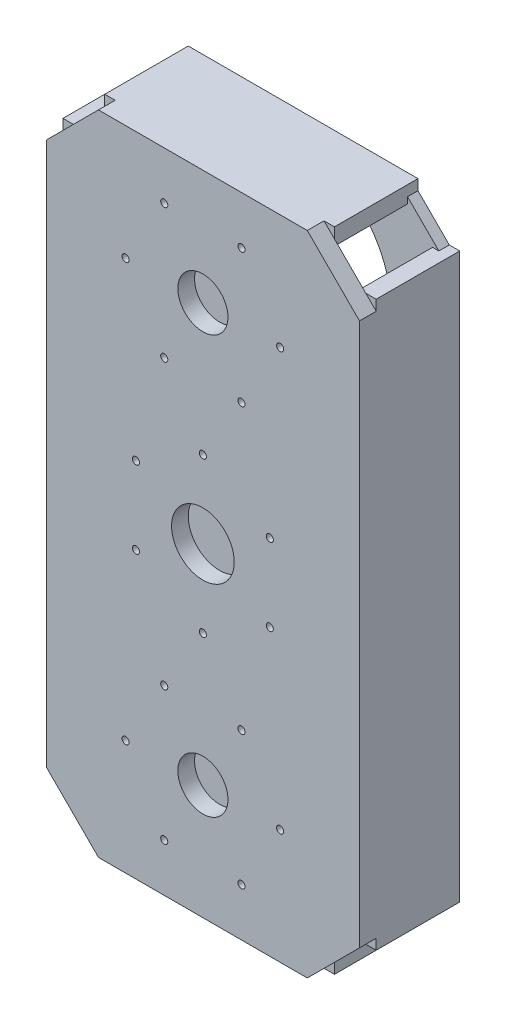
SolidWorks part; units mm, degrees
ref_plane "Front Plane" through (0, 0, 0) normal (0, 0, 1) x (1, 0, 0)
ref_plane "Top Plane" through (0, 0, 0) normal (0, 1, 0) x (1, 0, 0)
ref_plane "Right Plane" through (0, 0, 0) normal (1, 0, 0) x (0, 0, -1)
ref_plane "PL_Top_Plate_base" through (0, 0, 131) normal (0, 0, 1) x (1, 0, 0)
sketch "SK_Top_Plate" plane through (0, 0, 131) normal (0, 0, 1) x (1, 0, 0)
  line L0 (-50, -155) -> (50, -155)
  line L1 (50, -155) -> (75, -130)
  line L2 (75, -130) -> (75, 130)
  line L3 (75, 130) -> (50, 155)
  line L4 (50, 155) -> (-50, 155)
  line L5 (-50, 155) -> (-75, 130)
  line L6 (-75, 130) -> (-75, -130)
  line L7 (-75, -130) -> (-50, -155)
  circle A0 centre (37, 100) radius 1.7
  circle A1 centre (18.5, 132.0429) radius 1.7
  circle A2 centre (-18.5, 132.0429) radius 1.7
  circle A3 centre (-37, 100) radius 1.7
  circle A4 centre (-18.5, 67.9571) radius 1.7
  circle A5 centre (18.5, 67.9571) radius 1.7
  circle A6 centre (0, 100) radius 12
  circle A7 centre (37, -100) radius 1.7
  circle A8 centre (18.5, -67.9571) radius 1.7
  circle A9 centre (-18.5, -67.9571) radius 1.7
  circle A10 centre (-37, -100) radius 1.7
  circle A11 centre (-18.5, -132.0429) radius 1.7
  circle A12 centre (18.5, -132.0429) radius 1.7
  circle A13 centre (0, -100) radius 12
  circle A14 centre (32.0429, 18.5) radius 1.7
  circle A15 centre (0, 37) radius 1.7
  circle A16 centre (-32.0429, 18.5) radius 1.7
  circle A17 centre (-32.0429, -18.5) radius 1.7
  circle A18 centre (0, -37) radius 1.7
  circle A19 centre (32.0429, -18.5) radius 1.7
  circle A20 centre (0, 0) radius 15
  dimension "D17_SK_Top_Plate" = 3.4
  dimension "D20_SK_Top_Plate" = 3.4
  dimension "D23_SK_Top_Plate" = 3.4
  dimension "D26_SK_Top_Plate" = 3.4
  dimension "D29_SK_Top_Plate" = 3.4
  dimension "D32_SK_Top_Plate" = 3.4
  dimension "D35_SK_Top_Plate" = 24
  dimension "D37_SK_Top_Plate" = 3.4
  dimension "D40_SK_Top_Plate" = 3.4
  dimension "D43_SK_Top_Plate" = 3.4
  dimension "D46_SK_Top_Plate" = 3.4
  dimension "D49_SK_Top_Plate" = 3.4
  dimension "D52_SK_Top_Plate" = 3.4
  dimension "D55_SK_Top_Plate" = 24
  dimension "D57_SK_Top_Plate" = 3.4
  dimension "D60_SK_Top_Plate" = 3.4
  dimension "D62_SK_Top_Plate" = 3.4
  dimension "D65_SK_Top_Plate" = 3.4
  dimension "D68_SK_Top_Plate" = 3.4
  dimension "D70_SK_Top_Plate" = 3.4
  dimension "D73_SK_Top_Plate" = 30
  dimension "P1" = 50
  dimension "P2" = 155
  dimension "P3" = 50
  dimension "P4" = 155
  dimension "P5" = 75
  dimension "P6" = 130
  dimension "P7" = 75
  dimension "P8" = 130
  dimension "P9" = 50
  dimension "P10" = 155
  dimension "P11" = 50
  dimension "P12" = 155
  dimension "P13" = 75
  dimension "P14" = 130
  dimension "P15" = 75
  dimension "P16" = 130
  dimension "P18" = 37
  dimension "P19" = 100
  dimension "P21" = 18.5
  dimension "P22" = 132.0429
  dimension "P24" = 18.5
  dimension "P25" = 132.0429
  dimension "P27" = 37
  dimension "P28" = 100
  dimension "P30" = 18.5
  dimension "P31" = 67.9571
  dimension "P33" = 18.5
  dimension "P34" = 67.9571
  dimension "P36" = 100
  dimension "P38" = 37
  dimension "P39" = 100
  dimension "P41" = 18.5
  dimension "P42" = 67.9571
  dimension "P44" = 18.5
  dimension "P45" = 67.9571
  dimension "P47" = 37
  dimension "P48" = 100
  dimension "P50" = 18.5
  dimension "P51" = 132.0429
  dimension "P53" = 18.5
  dimension "P54" = 132.0429
  dimension "P56" = 100
  dimension "P58" = 32.0429
  dimension "P59" = 18.5
  dimension "P61" = 37
  dimension "P63" = 32.0429
  dimension "P64" = 18.5
  dimension "P66" = 32.0429
  dimension "P67" = 18.5
  dimension "P69" = 37
  dimension "P71" = 32.0429
  dimension "P72" = 18.5
extrude "Top_Plate" add sketch "SK_Top_Plate" along normal blind 8
ref_plane "PL_Front_Wall_base" through (67, 0, 0) normal (1, 0, 0) x (0, 0, -1)
sketch "SK_Front_Wall" plane through (67, 0, 0) normal (1, 0, 0) x (0, 0, -1)
  line L0 (-91, -135) -> (-91, 135)
  line L1 (-91, 135) -> (-131, 135)
  line L2 (-131, 135) -> (-131, -135)
  line L3 (-131, -135) -> (-91, -135)
  dimension "P1" = 91
  dimension "P2" = 135
  dimension "P3" = 91
  dimension "P4" = 135
  dimension "P5" = 131
  dimension "P6" = 135
  dimension "P7" = 131
  dimension "P8" = 135
extrude "Front_Wall" add sketch "SK_Front_Wall" along normal blind 8
ref_plane "PL_Back_Wall_base" through (-75, 0, 0) normal (1, 0, 0) x (0, 0, -1)
sketch "SK_Back_Wall" plane through (-75, 0, 0) normal (1, 0, 0) x (0, 0, -1)
  line L0 (-91, -135) -> (-91, 135)
  line L1 (-91, 135) -> (-131, 135)
  line L2 (-131, 135) -> (-131, -135)
  line L3 (-131, -135) -> (-91, -135)
  dimension "P1" = 91
  dimension "P2" = 135
  dimension "P3" = 91
  dimension "P4" = 135
  dimension "P5" = 131
  dimension "P6" = 135
  dimension "P7" = 131
  dimension "P8" = 135
extrude "Back_Wall" add sketch "SK_Back_Wall" along normal blind 8
ref_plane "PL_Left_Wall_base" through (0, 147, 0) normal (0, 1, 0) x (1, 0, 0)
sketch "SK_Left_Wall" plane through (0, 147, 0) normal (0, 1, 0) x (1, 0, 0)
  line L0 (-55, -91) -> (55, -91)
  line L1 (55, -91) -> (55, -131)
  line L2 (55, -131) -> (-55, -131)
  line L3 (-55, -131) -> (-55, -91)
  dimension "P1" = 55
  dimension "P2" = 91
  dimension "P3" = 55
  dimension "P4" = 91
  dimension "P5" = 55
  dimension "P6" = 131
  dimension "P7" = 55
  dimension "P8" = 131
extrude "Left_Wall" add sketch "SK_Left_Wall" along normal blind 8
ref_plane "PL_Right_Wall_base" through (0, -155, 0) normal (0, 1, 0) x (1, 0, 0)
sketch "SK_Right_Wall" plane through (0, -155, 0) normal (0, 1, 0) x (1, 0, 0)
  line L0 (-55, -91) -> (55, -91)
  line L1 (55, -91) -> (55, -131)
  line L2 (55, -131) -> (-55, -131)
  line L3 (-55, -131) -> (-55, -91)
  dimension "P1" = 55
  dimension "P2" = 91
  dimension "P3" = 55
  dimension "P4" = 91
  dimension "P5" = 55
  dimension "P6" = 131
  dimension "P7" = 55
  dimension "P8" = 131
extrude "Right_Wall" add sketch "SK_Right_Wall" along normal blind 8
ref_plane "PL_Bottom_Plate_base" through (0, 0, 91) normal (0, 0, 1) x (1, 0, 0)
sketch "SK_Bottom_Plate" plane through (0, 0, 91) normal (0, 0, 1) x (1, 0, 0)
  line L0 (-50, -155) -> (50, -155)
  line L1 (50, -155) -> (75, -130)
  line L2 (75, -130) -> (75, 130)
  line L3 (75, 130) -> (50, 155)
  line L4 (50, 155) -> (-50, 155)
  line L5 (-50, 155) -> (-75, 130)
  line L6 (-75, 130) -> (-75, -130)
  line L7 (-75, -130) -> (-50, -155)
  circle A0 centre (0, 100) radius 47
  circle A1 centre (0, -100) radius 47
  circle A2 centre (0, 0) radius 20
  dimension "D17_SK_Bottom_Plate" = 94
  dimension "D19_SK_Bottom_Plate" = 94
  dimension "D21_SK_Bottom_Plate" = 40
  dimension "P1" = 50
  dimension "P2" = 155
  dimension "P3" = 50
  dimension "P4" = 155
  dimension "P5" = 75
  dimension "P6" = 130
  dimension "P7" = 75
  dimension "P8" = 130
  dimension "P9" = 50
  dimension "P10" = 155
  dimension "P11" = 50
  dimension "P12" = 155
  dimension "P13" = 75
  dimension "P14" = 130
  dimension "P15" = 75
  dimension "P16" = 130
  dimension "P18" = 100
  dimension "P20" = 100
extrude "Bottom_Plate" add sketch "SK_Bottom_Plate" along normal blind 5
equation "\"Hip_spacing\" = 200"
equation "\"Pelvis_half_width\" = 155"
equation "\"Pelvis_half_depth\" = 75"
